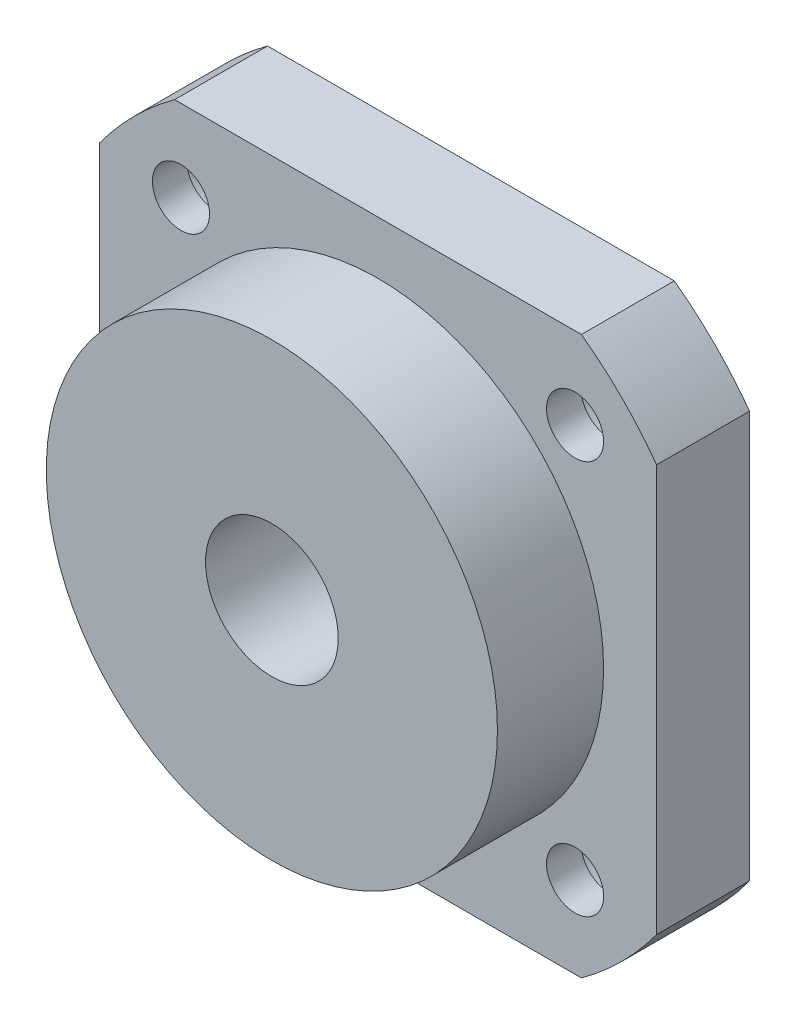
SolidWorks part; units mm, degrees
ref_plane "Front Plane" through (0, 0, 0) normal (0, 0, 1) x (1, 0, 0)
ref_plane "Top Plane" through (0, 0, 0) normal (0, 1, 0) x (1, 0, 0)
ref_plane "Right Plane" through (0, 0, 0) normal (1, 0, 0) x (0, 0, -1)
sketch "Sketch1" plane through (0, 0, 0) normal (0, 0, 1) x (1, 0, 0)
  line L1 (15.3297, -21) -> (-15.3297, -21)
  line L2 (21, -15.3297) -> (21, 15.3297)
  line L3 (15.3297, 21) -> (-15.3297, 21)
  line L4 (-21, -15.3297) -> (-21, 15.3297)
  line L5 (18.3848, -18.3848) -> (-21, 21) construction
  line L6 (18.3848, 18.3848) -> (-18.3848, -18.3848) construction
  arc A0 (-15.3297, 21) -> (-21, 15.3297) centre (0, 0) ccw
  arc A1 (-21, -15.3297) -> (-15.3297, -21) centre (0, 0) ccw
  arc A2 (15.3297, -21) -> (21, -15.3297) centre (0, 0) ccw
  arc A3 (21, 15.3297) -> (15.3297, 21) centre (0, 0) ccw
  circle A4 centre (0, 0) radius 5
  point P0 (0, 0)
  point P3 (-14.8492, 14.8492)
  point P19 (14.8492, 14.8492)
  point P20 (14.8492, -14.8492)
  point P21 (-14.8492, -14.8492)
  point P22 (0, 0)
  dimension "D3" = 52
  dimension "D4" = 10
  dimension "D1" = 21
  dimension "D2" = 4
extrude "Boss-Extrude1" add sketch "Sketch1" along normal blind 15
sketch "Sketch2" plane through (0, 0, 15) normal (0, 0, 1) x (1, 0, 0)
  circle A0 centre (0, 0) radius 17
  dimension "D1" = 34
extrude "Cut-Extrude-Thin1" cut sketch "Sketch2" against normal blind 8 thin thin type one direction wall 10
sketch "Sketch6" plane through (0, 0, 0) normal (0, 0, -1) x (-1, 0, 0)
  line L0 (0, 0) -> (-21, 0) construction
  line L1 (-21, -15.3297) -> (-21, 15.3297) construction
  line L2 (0, 0) -> (-18.3848, 18.3848) construction
  arc A0 (-15.3297, 21) -> (-21, 15.3297) centre (0, 0) ccw construction
  point P5 (-14.8492, 14.8492)
  point P13 (14.8492, 14.8492)
  point P14 (14.8492, -14.8492)
  point P15 (-14.8492, -14.8492)
  point P16 (0, 0)
  dimension "D1" = 21
  dimension "D2" = 4
hole_wizard "CBORE for M4 Hex Socket Head Cap Screw1" positions "3DSketch4" profile "Sketch8" counterbore size "M4" standard "ISO"
sketch3d "3DSketch4"
  point P0 (-14.8492, 14.8492, 0)
sketch "Sketch8" plane through (-14.8492, 14.8492, 0) normal (1, 0, 0) x (0, 1, 0)
  line L0 (0, 0) -> (0, 9.7919)
  line L1 (0, 9.7919) -> (2.15, 8.5)
  line L2 (2.15, 8.5) -> (2.15, 4.4)
  line L3 (2.15, 4.4) -> (4, 4.4)
  line L4 (4, 4.4) -> (4, 0)
  line L5 (4, 0) -> (0, 0)
  line L10 (0, 9.7919) -> (-2.15, 8.5) construction
  line L11 (0, -6.35) -> (0, 107.95) construction
  dimension "Hole Dia." = 4.3
  dimension "Hole Depth" = 8.5
  dimension "C'Bore Dia." = 8
  dimension "C'Bore Depth" = 4.4
  dimension "Drill Angle" = 118
hole_wizard "CBORE for M4 Hex Socket Head Cap Screw2" positions "3DSketch6" profile "Sketch10" counterbore size "M4" standard "ISO"
sketch3d "3DSketch6"
  point P0 (14.8492, 14.8492, 0)
sketch "Sketch10" plane through (14.8492, 14.8492, 0) normal (1, 0, 0) x (0, 1, 0)
  line L0 (0, 0) -> (0, 9.7919)
  line L1 (0, 9.7919) -> (2.15, 8.5)
  line L2 (2.15, 8.5) -> (2.15, 4.4)
  line L3 (2.15, 4.4) -> (4, 4.4)
  line L4 (4, 4.4) -> (4, 0)
  line L5 (4, 0) -> (0, 0)
  line L10 (0, 9.7919) -> (-2.15, 8.5) construction
  line L11 (0, -6.35) -> (0, 107.95) construction
  dimension "Hole Dia." = 4.3
  dimension "Hole Depth" = 8.5
  dimension "C'Bore Dia." = 8
  dimension "C'Bore Depth" = 4.4
  dimension "Drill Angle" = 118
hole_wizard "CBORE for M4 Hex Socket Head Cap Screw3" positions "3DSketch7" profile "Sketch11" counterbore size "M4" standard "ISO"
sketch3d "3DSketch7"
  point P0 (14.8492, -14.8492, 0)
sketch "Sketch11" plane through (14.8492, -14.8492, 0) normal (1, 0, 0) x (0, 1, 0)
  line L0 (0, 0) -> (0, 9.7919)
  line L1 (0, 9.7919) -> (2.15, 8.5)
  line L2 (2.15, 8.5) -> (2.15, 4.4)
  line L3 (2.15, 4.4) -> (4, 4.4)
  line L4 (4, 4.4) -> (4, 0)
  line L5 (4, 0) -> (0, 0)
  line L10 (0, 9.7919) -> (-2.15, 8.5) construction
  line L11 (0, -6.35) -> (0, 107.95) construction
  dimension "Hole Dia." = 4.3
  dimension "Hole Depth" = 8.5
  dimension "C'Bore Dia." = 8
  dimension "C'Bore Depth" = 4.4
  dimension "Drill Angle" = 118
hole_wizard "CBORE for M4 Hex Socket Head Cap Screw4" positions "3DSketch8" profile "Sketch12" counterbore size "M4" standard "ISO"
sketch3d "3DSketch8"
  point P0 (-14.8492, -14.8492, 0)
sketch "Sketch12" plane through (-14.8492, -14.8492, 0) normal (1, 0, 0) x (0, 1, 0)
  line L0 (0, 0) -> (0, 9.7919)
  line L1 (0, 9.7919) -> (2.15, 8.5)
  line L2 (2.15, 8.5) -> (2.15, 4.4)
  line L3 (2.15, 4.4) -> (4, 4.4)
  line L4 (4, 4.4) -> (4, 0)
  line L5 (4, 0) -> (0, 0)
  line L10 (0, 9.7919) -> (-2.15, 8.5) construction
  line L11 (0, -6.35) -> (0, 107.95) construction
  dimension "Hole Dia." = 4.3
  dimension "Hole Depth" = 8.5
  dimension "C'Bore Dia." = 8
  dimension "C'Bore Depth" = 4.4
  dimension "Drill Angle" = 118
